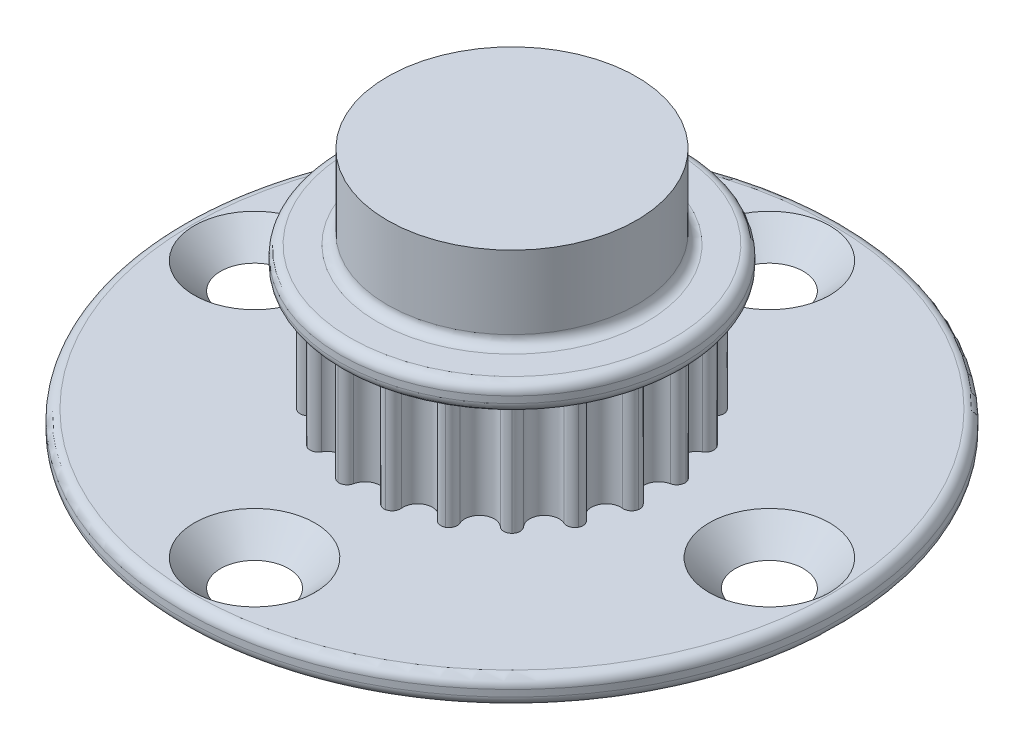
SolidWorks part; units mm, degrees
ref_plane "Front Plane" through (0, 0, 0) normal (0, 0, 1) x (1, 0, 0)
ref_plane "Top Plane" through (0, 0, 0) normal (0, 1, 0) x (1, 0, 0)
ref_plane "Right Plane" through (0, 0, 0) normal (1, 0, 0) x (0, 0, -1)
sketch "Sketch1" plane through (0, 0, 0) normal (0, 1, 0) x (1, 0, 0)
  line L0 (0, 0) -> (0, 9.1676) construction
  line L1 (0, 0) -> (2.731, 8.405) construction
  circle A0 centre (0, 0) radius 9.1676 construction
  circle A1 centre (0, 0) radius 7.9476 construction
  circle A2 centre (0, 8.8376) radius 0.89 construction
  circle A5 centre (2.731, 8.405) radius 0.89 construction
  arc A6 (0, 7.9476) -> (0.8721, 8.6598) centre (0, 8.8376) ccw
  arc A7 (0.8721, 8.6598) -> (1.4405, 9.0537) centre (1.362, 8.5599) cw
  arc A8 (1.4277, 9.0557) -> (1.8466, 8.5054) centre (1.3498, 8.5618) cw
  arc A9 (2.4559, 7.5586) -> (1.8466, 8.5054) centre (2.731, 8.405) cw
  arc A10 (1.4405, 9.0537) -> (1.4277, 9.0557) centre (0, 0) cw
  arc A11 (0, 7.9476) -> (2.4559, 7.5586) centre (0, 0) ccw
  dimension "D1" = 18.3352
  dimension "D3" = 1.78
  dimension "D4" = 0.5
  dimension "D2" = 1.22
  dimension "D5" = 18
extrude "Boss-Extrude1" add sketch "Sketch1" along normal mid plane 7.112 contours A6 A11 A9 A8 A7 region at (0.0089, 0, -0.0564)
ref_axis "Axis1" through (0, 3.3, 0) along (0, -1, 0)
pattern_circular "CirPattern1" count 20 over 360 about axis through (0, 3.3, 0) along (0, -1, 0) of "Boss-Extrude1"
sketch "Sketch2" plane through (0, 0, 0) normal (1, 0, 0) x (0, 0, -1)
  line L10 (0, 3.5) -> (10.3423, 3.5) construction
  line L11 (0, 3.5) -> (0, 5.0875) construction
  line L12 (0, 5.0875) -> (10.3423, 5.0875)
  line L15 (10.3423, 3.5) -> (10.3423, 5.0875) construction
  line L20 (0, 3.3) -> (0, -3.3) construction
  line L22 (10.3423, 5.0875) -> (0, 5.0875) construction
  line L23 (10.3423, 5.0875) -> (10.3423, 3.5)
  line L24 (10.3423, 3.5) -> (0, 3.5)
  line L25 (0, 5.0875) -> (0, 3.5)
  point P6 (0, 0)
  point P7 (6.9267, 5.0875)
  point P9 (7.5, 11.0603)
  dimension "D1" = 1.5875
  dimension "D2" = 10.3423
  dimension "D3" = 3.5
revolve "Revolve3" add sketch "Sketch2" angle 360 about axis through (0, 3.3, 0) along (0, -1, 0) region at (0, 4.2937, -5.1712)
mirror "Mirror1" about plane through (0, 0, 0) normal (0, 1, 0) of "Revolve3"
sketch "Sketch9" plane through (0, -5.0875, 0) normal (0, -1, 0) x (1, 0, 0)
  circle A0 centre (0, 0) radius 19.8438
  circle A1 centre (0, 0) radius 1.5
  point P4 (0, 0)
  dimension "D1" = 3
  dimension "D2" = 39.6875
extrude "Boss-Extrude2" add sketch "Sketch9" against normal up to surface (1.5875 mm away) up to face at (0, -3.5, 0)
sketch "Sketch3" plane through (0, 0, 0) normal (0, 1, 0) x (1, 0, 0)
  circle A0 centre (-15.5, 0) radius 1.7462
  circle A3 centre (0, 15.5) radius 1.7462
  circle A4 centre (15.5, 0) radius 1.7463
  circle A5 centre (0, -15.5) radius 1.7462
  dimension "D3" = 3.4925
  dimension "D1" = 15.5
  dimension "D4" = 4
extrude "Cut-Extrude1" cut sketch "Sketch3" against normal through all both and the other way through all
ref_axis "Axis2" through (-15.5, -5.0875, 0) along (0, 1, 0)
sketch "Sketch6" plane through (0, 0, 0) normal (0, 0, 1) x (1, 0, 0)
  line L0 (-19.1322, -3.5) -> (-11.8678, -3.5) construction
  line L1 (-13.7538, -3.5) -> (-17.2462, -3.5) construction
  line L2 (-11.8678, -3.5) -> (-15.5, -7.1322)
  line L3 (-15.5, -7.1322) -> (-19.1322, -3.5) construction
  line L4 (-18.548, -4.0842) -> (-12.452, -4.0842) construction
  line L5 (-17.2462, -3.998) -> (-13.7538, -3.998) construction
  line L8 (-15.5, -7.1322) -> (-15.5, -3.5)
  line L9 (-15.5, -3.5) -> (-11.8678, -3.5)
  line L10 (-15.5, -5.0875) -> (-15.5, -3.5) construction
  line L12 (-17.2462, -3.5) -> (-17.2462, -5.0875) construction
  line L13 (-13.7538, -5.0875) -> (-13.7538, -3.5) construction
  point P2 (-15.5, -3.998)
  dimension "D1" = 6.096
  dimension "D2" = 0.5842
revolve "Cut-Revolve2" cut sketch "Sketch6" angle 360 about axis through (-15.5, -5.0875, 0) along (0, 1, 0)
pattern_circular "CirPattern2" count 4 over 360 about axis through (0, 3.3, 0) along (0, -1, 0) of "Cut-Revolve2"
sketch "Sketch10" plane through (0, 0, 0) normal (1, 0, 0) x (0, 0, -1)
  line L0 (10.3423, 5.0875) -> (-10.3423, 5.0875) construction
  line L1 (0, 5.0875) -> (7.5, 5.0875)
  line L2 (0, 5.0875) -> (0, 10.0875)
  line L3 (0, 10.0875) -> (7.5, 10.0875)
  line L4 (7.5, 5.0875) -> (7.5, 10.0875)
  line L5 (0, 5.0875) -> (0, 0) construction
  dimension "D1" = 15
  dimension "D2" = 5
revolve "Revolve4" add sketch "Sketch10" angle 360 about L5
fillet "Fillet1" radius 0.5953 5 edges at (0, 5.0875, 7.5) (0, 5.0875, 10.3423) (0, 3.5, 10.3423) (0, -3.5, 19.8438) (0, -5.0875, -19.8438)
equation "\"TEETH_NUM\"= 20"
equation "\"TOOTH_PITCH\"= 3mm"
equation "\"PITCH_LINE_OFFSET\"= .015in"
equation "\"DIAMETER_PER_GROOVE\"= \"OUTSIDE_DIAMETER\" / \"TEETH_NUM\" * 1in"
equation "\"PITCH_DIAMETER\"= ( ( \"TEETH_NUM\" * 3 - 1.31 ) / 3.1415 + .415 ) * 1mm"
equation "\"OUTSIDE_DIAMETER\"= \"PITCH_DIAMETER\" - \"PITCH_LINE_OFFSET\" * 2"
equation "\"D1@Sketch1\"=\"OUTSIDE_DIAMETER\""
equation "\"TOOTH_HEIGHT\"= 1.22mm"
equation "\"D2@Sketch1\"=\"TOOTH_HEIGHT\""
equation "\"TOOTH_DIAMETER\"= 1.78mm"
equation "\"INTERNAL_RADIUS\"= .5mm"
equation "\"D3@Sketch1\"=\"TOOTH_DIAMETER\""
equation "\"D5@Sketch1\"=360 / \"TEETH_NUM\""
equation "\"D4@Sketch1\"=\"INTERNAL_RADIUS\""
equation "\"D1@CirPattern1\"=\"TEETH_NUM\""
equation "\"BELT_GAP\"= 7mm"
equation "\"D2@Sketch2\"=\"PITCH_DIAMETER\"/2+1/32"
equation "\"D3@Sketch2\"=\"BELT_GAP\"/2"
